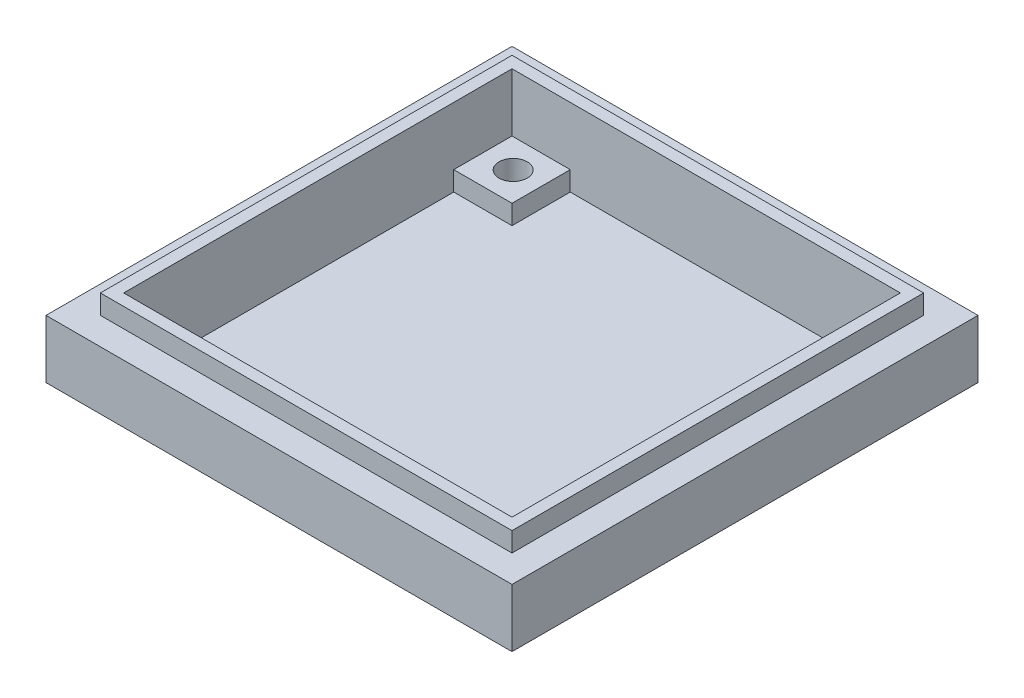
SolidWorks part; units mm, degrees
ref_plane "Front" through (0, 0, 0) normal (0, 0, 1) x (1, 0, 0)
ref_plane "Top" through (0, 0, 0) normal (0, 1, 0) x (1, 0, 0)
ref_plane "Right" through (0, 0, 0) normal (1, 0, 0) x (0, 0, -1)
sketch "Sketch1" plane through (0, 0, 0) normal (0, 1, 0) x (1, 0, 0)
  line L0 (-19.2823, 25.5161) -> (86.7177, 25.5161)
  line L1 (-26.2823, 32.5161) -> (93.7177, 32.5161)
  line L2 (-26.2823, 32.5161) -> (-26.2823, -87.4839)
  line L3 (-26.2823, -87.4839) -> (93.7177, -87.4839)
  line L4 (93.7177, 32.5161) -> (93.7177, -87.4839)
  line L5 (33.7177, -87.4839) -> (33.7177, 32.5161) construction
  line L6 (-26.2823, -27.4839) -> (93.7177, -27.4839) construction
  line L11 (86.7177, 25.5161) -> (86.7177, -80.4839)
  line L12 (-19.2823, -80.4839) -> (86.7177, -80.4839)
  line L13 (-19.2823, 25.5161) -> (-19.2823, -80.4839)
  line L14 (-16.2823, 22.5161) -> (83.7177, 22.5161)
  line L15 (83.7177, 22.5161) -> (83.7177, -77.4839)
  line L16 (-16.2823, -77.4839) -> (83.7177, -77.4839)
  line L17 (-16.2823, 22.5161) -> (-16.2823, -77.4839)
  line L18 (-17.7823, 24.0161) -> (85.2177, 24.0161)
  line L19 (85.2177, 24.0161) -> (85.2177, -78.9839)
  line L20 (-17.7823, -78.9839) -> (85.2177, -78.9839)
  line L21 (-17.7823, 24.0161) -> (-17.7823, -78.9839)
  point P248 (33.7177, -27.4839)
  dimension "D1" = 120
  dimension "D2" = 7
  dimension "D3" = 3
  dimension "D4" = 8.5
extrude "Boss-Extrude1" add sketch "Sketch1" along normal blind 20 contours L4 L1 L2 L3 L13 L0 L11 L12 region at (33.7177, 0, -30.8191)
extrude "Boss-Extrude2" add sketch "Sketch1<4>" along normal blind 25 contours L0 L13 L12 L11 L21 L18 L19 L20 | L14 L17 L16 L15 | L21 L20 L19 L18 region at (33.7177, 0, -24.0171) region at (33.7177, 0, 27.4839)
sketch "Sketch1<4>" plane through (0, 0, 0) normal (0, 1, 0) x (1, 0, 0) same geometry as "Sketch1"
extrude "Boss-Extrude3" add sketch "Sketch1<5>" along normal blind 5 contours L14 L17 L16 L15 region at (33.7177, 0, 27.4839)
sketch "Sketch1<5>" plane through (0, 0, 0) normal (0, 1, 0) x (1, 0, 0) same geometry as "Sketch1"
extrude "Cut-Extrude1" cut sketch "Sketch1<7>" along normal blind 2 contours L21 L20 L19 L18
sketch "Sketch1<7>" plane through (0, 0, 0) normal (0, 1, 0) x (1, 0, 0) same geometry as "Sketch1"
sketch "Sketch2" plane through (0, 5, 0) normal (0, 1, 0) x (1, 0, 0)
  line L0 (68.7177, 22.5161) -> (83.7177, 22.5161)
  line L1 (-16.2823, 22.5161) -> (-1.2823, 22.5161)
  line L2 (-16.2823, 22.5161) -> (-16.2823, 7.5161)
  line L3 (-16.2823, 7.5161) -> (-1.2823, 7.5161)
  line L4 (-1.2823, 22.5161) -> (-1.2823, 7.5161)
  line L5 (-8.7823, 7.5161) -> (-8.7823, 22.5161) construction
  line L6 (-16.2823, 15.0161) -> (-1.2823, 15.0161) construction
  line L7 (83.7177, 22.5161) -> (83.7177, 7.5161)
  line L8 (68.7177, 22.5161) -> (68.7177, 7.5161)
  line L9 (68.7177, 7.5161) -> (83.7177, 7.5161)
  line L10 (-16.2823, -62.4839) -> (-1.2823, -62.4839)
  line L11 (-1.2823, -62.4839) -> (-1.2823, -77.4839)
  line L12 (-16.2823, -62.4839) -> (-16.2823, -77.4839)
  line L13 (-16.2823, -77.4839) -> (-1.2823, -77.4839)
  line L14 (68.7177, -62.4839) -> (83.7177, -62.4839)
  line L15 (83.7177, -62.4839) -> (83.7177, -77.4839)
  line L16 (68.7177, -62.4839) -> (68.7177, -77.4839)
  line L17 (68.7177, -77.4839) -> (83.7177, -77.4839)
  point P12 (0, 0)
  point P136 (-8.7823, 15.0161)
  dimension "D1" = 15
extrude "Boss-Extrude5" add sketch "Sketch2" along normal blind 5
sketch "Sketch8" plane through (0, 5, 0) normal (0, 1, 0) x (1, 0, 0)
  circle A0 centre (-8.5622, 15.0905) radius 3.6439
  circle A1 centre (76.4378, 15.0905) radius 3.6439
  circle A2 centre (-8.5622, -69.9095) radius 3.6439
  circle A3 centre (76.4378, -69.9095) radius 3.6439
extrude "Cut-Extrude7" cut sketch "Sketch8" against normal through all and the other way blind 112
chamfer "Chamfer1" distance 5 angle 45 4 edges at (-26.2823, 0, 27.4839) (33.7177, 0, 87.4839) (93.7177, 0, 27.4839) (33.7177, 0, -32.5161)
